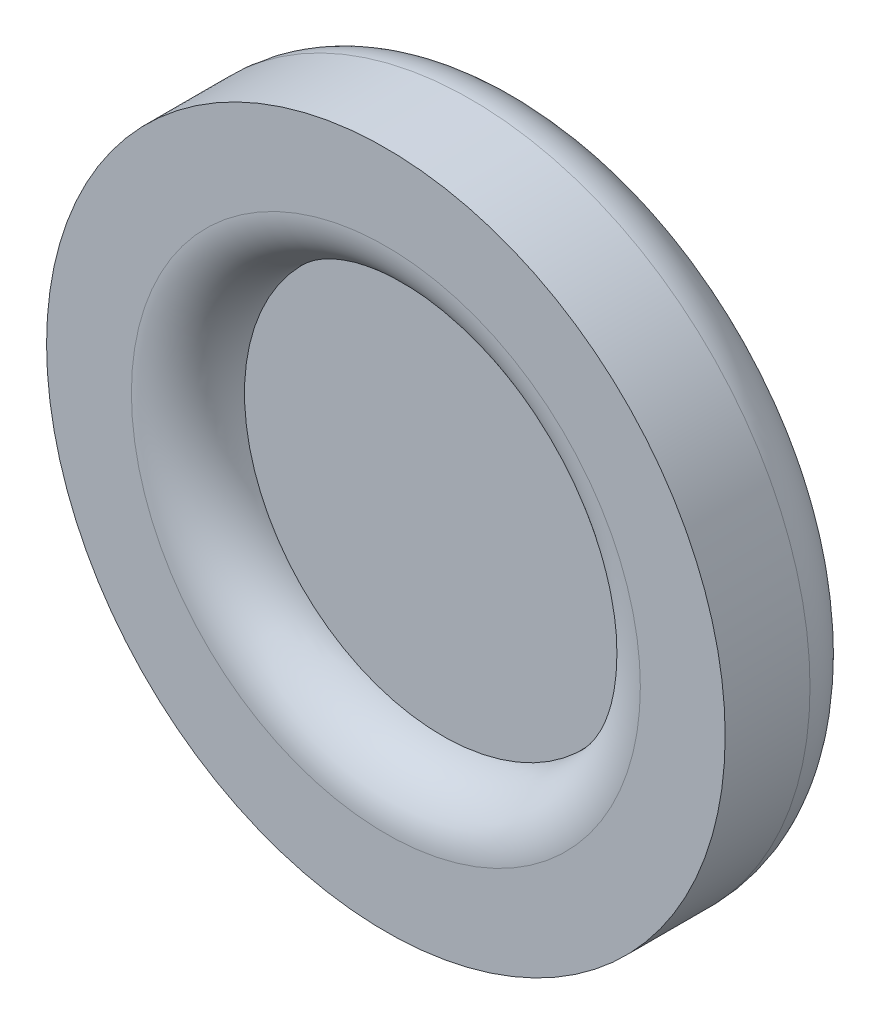
SolidWorks part; units mm, degrees
ref_plane "Ön Düzlem" through (0, 0, 0) normal (0, 0, 1) x (1, 0, 0)
ref_plane "Üst Düzlem" through (0, 0, 0) normal (0, 1, 0) x (1, 0, 0)
ref_plane "Sağ Düzlem" through (0, 0, 0) normal (1, 0, 0) x (0, 0, -1)
sketch "Çizim1" plane through (0, 0, 0) normal (0, 0, 1) x (1, 0, 0)
  circle A0 centre (0, 0) radius 6
  dimension "D1" = 12
extrude "Yükseklik-Ekstrüzyon1" add sketch "Çizim1" along normal blind 2.5
sketch "Çizim2" plane through (0, 0, 2.5) normal (0, 0, 1) x (1, 0, 0)
  circle A0 centre (0, 0) radius 3.5
  dimension "D1" = 7
extrude "Kes-Ekstrüzyon1" cut sketch "Çizim2" against normal blind 1
fillet "Radyus1" radius 1 2 edges at (6, 0, 0) (3.5, 0, 2.5)
sketch "Çizim3" plane through (0, 0, 0) normal (0, 0, -1) x (-1, 0, 0)
  line L0 (-3.7094, -2.3783) -> (3.7094, -2.3783) construction
  text T0 "SP" font "Century Schoolbook" height 4
  point P2 (0, -2.3783)
extrude "Kes-Ekstrüzyon2" cut sketch "Çizim3" against normal blind 0.75
